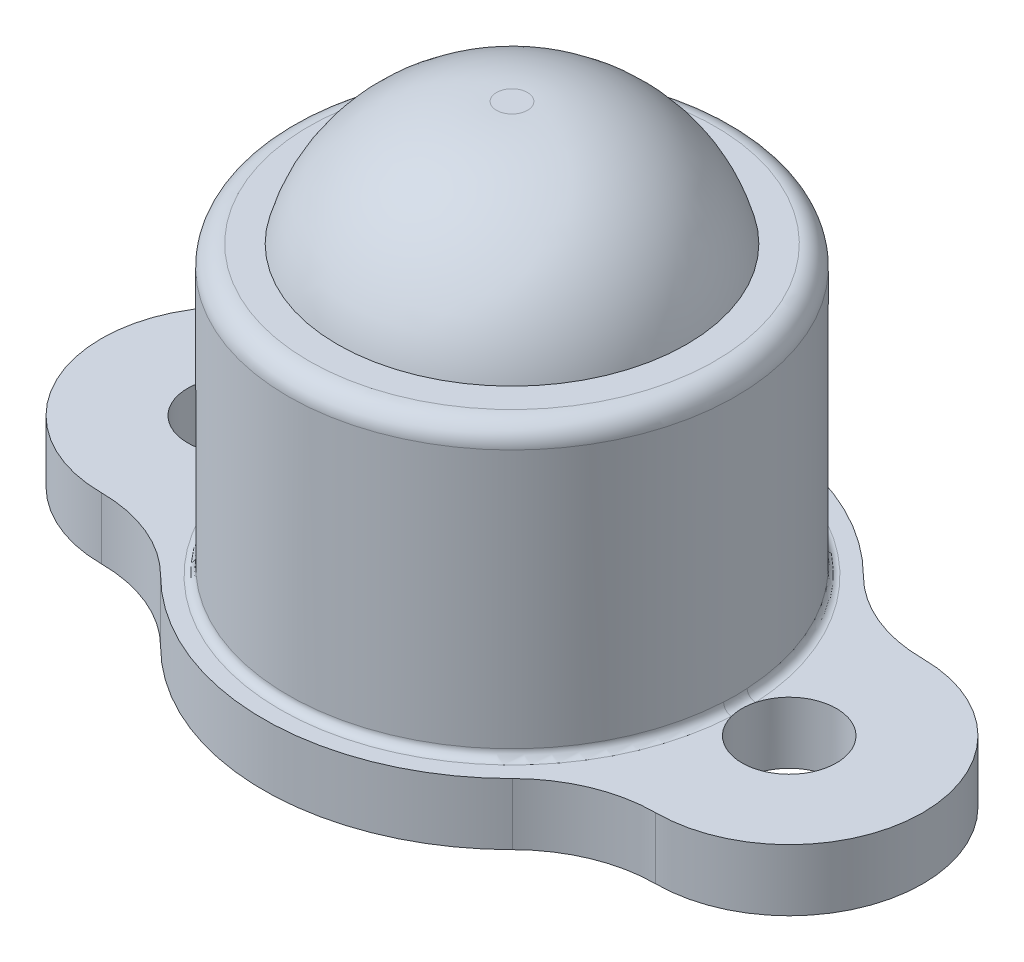
SolidWorks part; units mm, degrees
ref_plane "Front Plane" through (0, 0, 0) normal (0, 0, 1) x (1, 0, 0)
ref_plane "Top Plane" through (0, 0, 0) normal (0, 1, 0) x (1, 0, 0)
ref_plane "Right Plane" through (0, 0, 0) normal (1, 0, 0) x (0, 0, -1)
sketch "Sketch1" plane through (0, 0, 0) normal (0, 1, 0) x (1, 0, 0)
  line L0 (0, 0) -> (0, 6.05) construction
  line L1 (0, 0) -> (-3.5, 0) construction
  arc A0 (-4.2824, -4.2736) -> (4.2824, -4.2736) centre (0, 0) ccw
  circle A1 centre (0, 0) radius 2.9469
  arc A2 (-6.75, 3.25) -> (-6.75, -3.25) centre (-6.75, 0) ccw
  arc A3 (6.75, 3.25) -> (6.75, -3.25) centre (6.75, 0) cw
  arc A4 (-6.75, 3.25) -> (-4.2824, 4.2736) centre (-6.75, 6.7362) ccw
  arc A5 (-6.75, -3.25) -> (-4.2824, -4.2736) centre (-6.75, -6.7362) cw
  arc A6 (6.75, 3.25) -> (4.2824, 4.2736) centre (6.75, 6.7362) cw
  arc A7 (6.75, -3.25) -> (4.2824, -4.2736) centre (6.75, -6.7362) ccw
  arc A8 (4.2824, 4.2736) -> (-4.2824, 4.2736) centre (0, 0) ccw
  dimension "D1" = 12.1
  dimension "D2" = 5.8938
  dimension "D3" = 6.5
  dimension "D4" = 6.75
extrude "Boss-Extrude1" add sketch "Sketch1" along normal blind 1.5 contours A2 A0 | A0 A1 | A3 A0 region at (-5.3247, 0, 3.3001)
sketch "Sketch2" plane through (0, 1.5, 0) normal (0, 1, 0) x (1, 0, 0)
  line L0 (0, 0) -> (0, -6.05) construction
  circle A0 centre (-6.75, 0) radius 1.15
  arc A2 (-6.75, 3.25) -> (-6.75, -3.25) centre (-6.75, 0) ccw construction
  arc A3 (-4.2824, -4.2736) -> (4.2824, -4.2736) centre (0, 0) ccw construction
  circle A4 centre (6.75, 0) radius 1.15
  dimension "D1" = 2.3
extrude "Cut-Extrude1" cut sketch "Sketch2" against normal through all
sketch "Sketch3" plane through (0, 1.5, 0) normal (0, 1, 0) x (1, 0, 0)
  circle A2 centre (0, 0) radius 5.4469
  circle A3 centre (0, 0) radius 5.4469
  arc A4 (-6.75, 3.25) -> (-6.75, -3.25) centre (-6.75, 0) ccw
  arc A5 (-4.2824, -4.2736) -> (-6.75, -3.25) centre (-6.75, -6.7362) ccw
  arc A6 (6.75, -3.25) -> (6.75, 3.25) centre (6.75, 0) ccw
  arc A7 (-4.2824, -4.2736) -> (-6.75, -3.25) centre (-6.75, -6.7362) ccw
  arc A8 (-6.75, 3.25) -> (-6.75, -3.25) centre (-6.75, 0) ccw
  arc A9 (-4.2824, -4.2736) -> (4.2824, -4.2736) centre (0, 0) ccw
  arc A10 (6.75, -3.25) -> (6.75, 3.25) centre (6.75, 0) ccw
  arc A11 (-4.2824, -4.2736) -> (4.2824, -4.2736) centre (0, 0) ccw
  arc A18 (6.75, -3.25) -> (4.2824, -4.2736) centre (6.75, -6.7362) ccw
  arc A19 (6.75, -3.25) -> (4.2824, -4.2736) centre (6.75, -6.7362) ccw
  arc A20 (4.2824, 4.2736) -> (6.75, 3.25) centre (6.75, 6.7362) ccw
  arc A21 (4.2824, 4.2736) -> (6.75, 3.25) centre (6.75, 6.7362) ccw
  arc A22 (4.2824, 4.2736) -> (-4.2824, 4.2736) centre (0, 0) ccw
  arc A23 (4.2824, 4.2736) -> (-4.2824, 4.2736) centre (0, 0) ccw
  arc A24 (-6.75, 3.25) -> (-4.2824, 4.2736) centre (-6.75, 6.7362) ccw
  arc A25 (-6.75, 3.25) -> (-4.2824, 4.2736) centre (-6.75, 6.7362) ccw
  circle M20 centre (0, 0) radius 2.9469
  dimension "D1" = 0
  dimension "D2" = 2.5
extrude "Boss-Extrude2" add sketch "Sketch3" along normal blind 7 contours A3 M20 region at (-5.2928, 1.5, 0)
sketch "Sketch4" plane through (0, 8.5, 0) normal (0, 1, 0) x (1, 0, 0)
  circle A0 centre (0, 0) radius 4.25
  dimension "D1" = 8.5
extrude "Boss-Extrude3" add sketch "Sketch4" along normal blind 3
fillet "Fillet1" radius 4 1 edges at (0, 11.5, 4.25)
fillet "Fillet2" radius 0.5 1 edges at (0, 8.5, 5.4469)
fillet "Fillet3" radius 0.2 1 edges at (0, 1.5, 5.4469)
